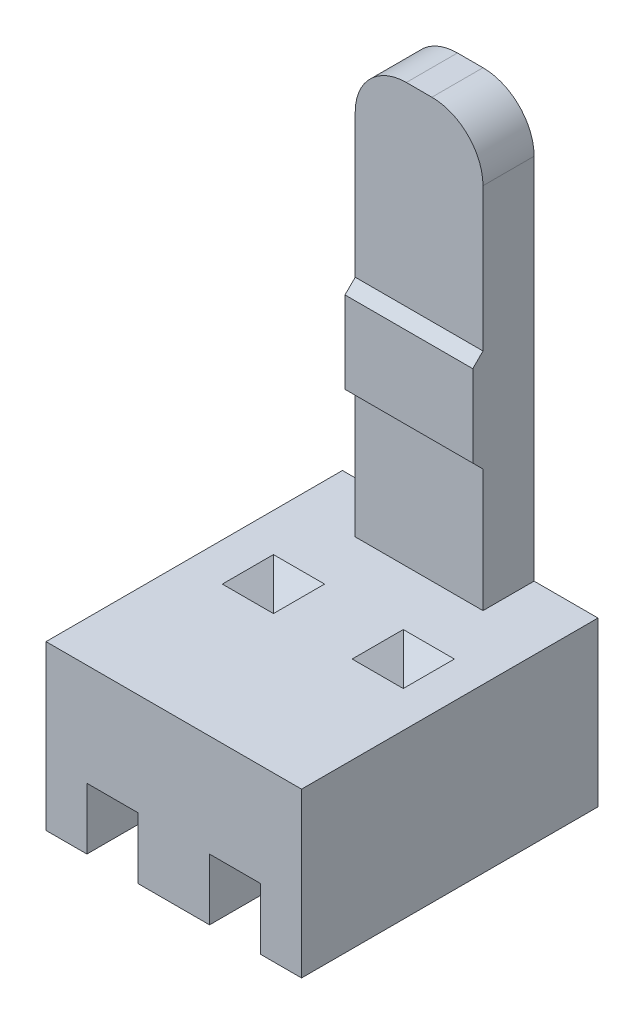
SolidWorks part; units mm, degrees
ref_plane "Спереди" through (0, 0, 0) normal (0, 0, 1) x (1, 0, 0)
ref_plane "Сверху" through (0, 0, 0) normal (0, 1, 0) x (1, 0, 0)
ref_plane "Справа" through (0, 0, 0) normal (1, 0, 0) x (0, 0, -1)
sketch "Эскиз1" plane through (0, 0, 0) normal (0, 0, 1) x (1, 0, 0)
  line L0 (0, 0) -> (0, 3.2)
  line L1 (0, 3.2) -> (5, 3.2)
  line L2 (5, 0) -> (4.2, 0)
  line L3 (4.2, 0) -> (4.2, 1.2)
  line L4 (4.2, 1.2) -> (3.2, 1.2)
  line L5 (3.2, 1.2) -> (3.2, 0)
  line L6 (3.2, 0) -> (1.8, 0)
  line L7 (1.8, 0) -> (1.8, 1.2)
  line L8 (1.8, 1.2) -> (0.8, 1.2)
  line L9 (0.8, 1.2) -> (0.8, 0)
  line L10 (0.8, 0) -> (0, 0)
  line L11 (5, 3.2) -> (5, 0)
  dimension "D1" = 5
  dimension "D2" = 0.8
  dimension "D3" = 1
  dimension "D4" = 1.4
  dimension "D5" = 1
  dimension "D6" = 3.2
  dimension "D7" = 1.2
extrude "Бобышка-Вытянуть1" add sketch "Эскиз1" along normal blind 5.8
sketch "Эскиз2" plane through (0, 3.2, 0) normal (0, 1, 0) x (1, 0, 0)
  line L0 (5, 0) -> (0, 0) construction
  line L1 (1.25, 0) -> (3.75, 0)
  line L2 (1.25, 0) -> (1.25, -1)
  line L3 (1.25, -1) -> (3.75, -1)
  line L4 (3.75, 0) -> (3.75, -1)
  line L5 (2.5, 0) -> (2.5, -5.8) construction
  line L6 (5, -5.8) -> (0, -5.8) construction
  dimension "D1" = 2.5
  dimension "D2" = 1
extrude "Бобышка-Вытянуть2" add sketch "Эскиз2" along normal blind 8.2
sketch "Эскиз3" plane through (0, 0, 1) normal (0, 0, 1) x (1, 0, 0)
  line L0 (1.25, 11.4) -> (1.25, 3.2) construction
  line L1 (1.25, 5.6) -> (3.75, 5.6)
  line L2 (1.25, 5.6) -> (1.25, 7.6)
  line L3 (1.25, 7.6) -> (3.75, 7.6)
  line L4 (3.75, 5.6) -> (3.75, 7.6)
  line L5 (3.75, 11.4) -> (3.75, 3.2) construction
  line L6 (1.25, 3.2) -> (3.75, 3.2) construction
  dimension "D1" = 2.4
  dimension "D2" = 2
extrude "Бобышка-Вытянуть3" add sketch "Эскиз3" along normal blind 0.2
chamfer "Фаска1" distance 0.2 angle 45 2 edges at (2.5, 5.6, 1.2) (2.5, 7.6, 1.2)
fillet "Скругление1" radius 1 2 edges at (1.25, 11.4, 0.5) (3.75, 11.4, 0.5)
sketch "Эскиз4" plane through (0, 3.2, 0) normal (0, 1, 0) x (1, 0, 0)
  line L0 (1.25, 0) -> (0, 0) construction
  line L1 (0.75, -2.1) -> (1.75, -2.1)
  line L2 (0.75, -2.1) -> (0.75, -3.1)
  line L3 (0.75, -3.1) -> (1.75, -3.1)
  line L4 (1.75, -2.1) -> (1.75, -3.1)
  line L5 (0, -5.8) -> (0, 0) construction
  dimension "D1" = 1
  dimension "D2" = 1
  dimension "D3" = 2.1
  dimension "D4" = 0.75
extrude "Вырез-Вытянуть1" cut sketch "Эскиз4" against normal blind 0.5 draft 44
pattern_linear "Линейный массив1" count 2 spacing 2.54 along (1, 0, 0) of "Вырез-Вытянуть1"
